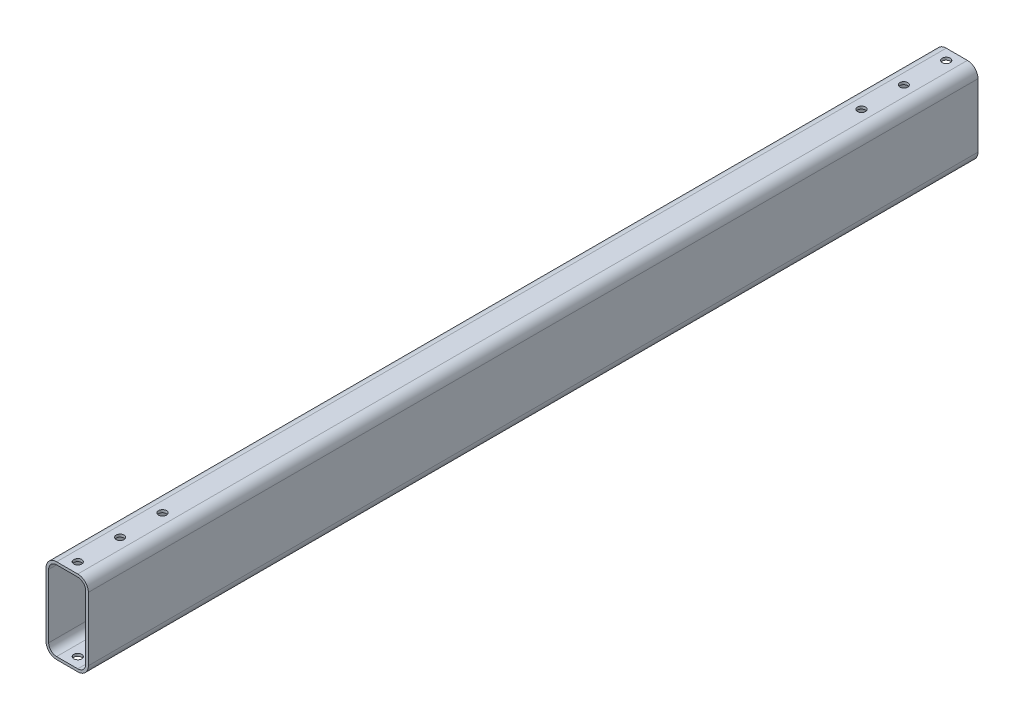
SolidWorks part; units mm, degrees
material "6061-T6 (SS)"
ref_plane "Front Plane" through (0, 0, 0) normal (0, 0, 1) x (1, 0, 0)
ref_plane "Top Plane" through (0, 0, 0) normal (0, 1, 0) x (1, 0, 0)
ref_plane "Right Plane" through (0, 0, 0) normal (1, 0, 0) x (0, 0, -1)
sketch "Sketch1" plane through (0, 0, 0) normal (0, 0, 1) x (1, 0, 0)
  line L1 (-6.35, -25.4) -> (6.35, -25.4)
  line L2 (-12.7, -19.05) -> (-12.7, 19.05)
  line L3 (-6.35, 25.4) -> (6.35, 25.4)
  line L4 (12.7, -19.05) -> (12.7, 19.05)
  line L5 (-12.7, -25.4) -> (12.7, 25.4) construction
  line L6 (-12.7, 25.4) -> (12.7, -25.4) construction
  arc A0 (-12.7, -19.05) -> (-6.35, -25.4) centre (-6.35, -19.05) ccw
  arc A1 (6.35, -25.4) -> (12.7, -19.05) centre (6.35, -19.05) ccw
  arc A2 (6.35, 25.4) -> (12.7, 19.05) centre (6.35, 19.05) cw
  arc A3 (-12.7, 19.05) -> (-6.35, 25.4) centre (-6.35, 19.05) cw
  point P0 (0, 0)
  dimension "D3" = 6.35
  dimension "D1" = 50.8
  dimension "D2" = 25.4
extrude "Extrude-Thin1" add sketch "Sketch1" along normal blind 533.4 thin thin type one direction reverse wall 1.5875
hole_wizard "3/16 (0.1875) Diameter Hole1" positions "3DSketch1" profile "Sketch3" hole size "3/16" standard "ANSI Inch" end condition through all
sketch3d "3DSketch1"
  line L1 (6.35, 25.4, 0) -> (-6.35, 25.4, 0) construction
  line L6 (0, 25.4, 533.4) -> (0, 25.4, 0) construction
  line L7 (6.35, 25.4, 533.4) -> (-6.35, 25.4, 533.4) construction
  point P57 (0, 25.4, 6.35)
  point P59 (0, 25.4, 31.75)
  point P61 (0, 25.4, 57.15)
  point P63 (0, 25.4, 501.65)
  point P65 (0, 25.4, 476.25)
  point P67 (0, 25.4, 527.05)
  dimension "D1" = 25.4
  dimension "D2" = 25.4
  dimension "D3" = 6.35
  dimension "D4" = 25.4
  dimension "D5" = 25.4
  dimension "D6" = 6.35
sketch "Sketch3" plane through (0, 25.4, 527.05) normal (1, 0, 0) x (0, 0, 1)
  line L0 (0, 0) -> (0, 50.8)
  line L1 (0, 50.8) -> (2.3812, 50.8)
  line L2 (2.3812, 50.8) -> (2.3812, 0)
  line L5 (2.3812, 0) -> (0, 0)
  line L11 (0, -6.35) -> (0, 107.95) construction
  dimension "Thru Hole Dia." = 4.7625
  dimension "Thru Hole Depth" = 50.8
